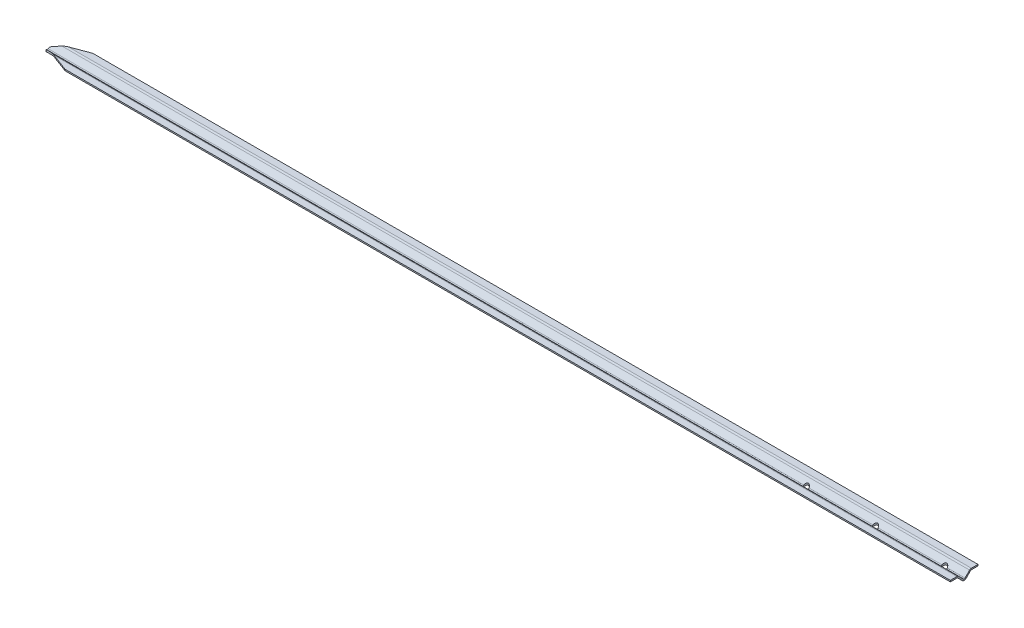
SolidWorks part; units mm, degrees
ref_plane "Спереди" through (0, 0, 0) normal (0, 0, 1) x (1, 0, 0)
ref_plane "Сверху" through (0, 0, 0) normal (0, 1, 0) x (1, 0, 0)
ref_plane "Справа" through (0, 0, 0) normal (1, 0, 0) x (0, 0, -1)
sketch "Эскиз1" plane through (0, 0, 0) normal (1, 0, 0) x (0, 0, -1)
  line L0 (-15, 0) -> (-7, 0)
  line L1 (-7, 0) -> (0, -7)
  line L2 (0, -7) -> (7, 0)
  line L3 (7, 0) -> (15, 0)
  line L4 (0, -3.8182) -> (0, 15.4545) construction
  dimension "D1" = 7
  dimension "D2" = 30
  dimension "D3" = 90
sketch "Эскиз5" plane through (0, 0, 0) normal (1, 0, 0) x (0, 0, -1)
  line L0 (-15, 0) -> (-7, 0) construction
  line L1 (-7, 0) -> (0, -7) construction
  line L2 (0, -7) -> (7, 0) construction
  line L3 (7, 0) -> (15, 0) construction
  line L4 (-15, 0) -> (-7.8284, 0) construction
  line L5 (-6.4142, -0.5858) -> (-1.4142, -5.5858) construction
  line L6 (1.4142, -5.5858) -> (6.4142, -0.5858) construction
  line L7 (7.8284, 0) -> (15, 0) construction
  line L8 (-15, -0.75) -> (-7.8284, -0.75)
  line L9 (-6.9445, -1.1161) -> (-1.9445, -6.1161)
  line L10 (1.9445, -6.1161) -> (6.9445, -1.1161)
  line L11 (7.8284, -0.75) -> (15, -0.75)
  line L12 (-15, 0.75) -> (-7.8284, 0.75)
  line L13 (-5.8839, -0.0555) -> (-0.8839, -5.0555)
  line L14 (0.8839, -5.0555) -> (5.8839, -0.0555)
  line L15 (7.8284, 0.75) -> (15, 0.75)
  line L16 (-15, -0.75) -> (-15, 0.75)
  line L17 (15, -0.75) -> (15, 0.75)
  arc A0 (-7.8284, 0) -> (-6.4142, -0.5858) centre (-7.8284, -2) cw construction
  arc A1 (-1.4142, -5.5858) -> (1.4142, -5.5858) centre (0, -4.1716) ccw construction
  arc A2 (6.4142, -0.5858) -> (7.8284, 0) centre (7.8284, -2) cw construction
  arc A3 (-7.8284, -0.75) -> (-6.9445, -1.1161) centre (-7.8284, -2) cw
  arc A4 (-1.9445, -6.1161) -> (1.9445, -6.1161) centre (0, -4.1716) ccw
  arc A5 (6.9445, -1.1161) -> (7.8284, -0.75) centre (7.8284, -2) cw
  arc A6 (-7.8284, 0.75) -> (-5.8839, -0.0555) centre (-7.8284, -2) cw
  arc A7 (-0.8839, -5.0555) -> (0.8839, -5.0555) centre (0, -4.1716) ccw
  arc A8 (5.8839, -0.0555) -> (7.8284, 0.75) centre (7.8284, -2) cw
  point P36 (-15, 0.75)
  dimension "D1" = 2
  dimension "D2" = 0.75
  dimension "D3" = 0.75
extrude "Бобышка-Вытянуть1" add sketch "Эскиз5" along normal mid plane 1000
sketch "Эскиз2" plane through (0, 0, 0) normal (0, 1, 0) x (1, 0, 0)
  line L0 (-500, 0) -> (-318.2949, 0) construction
  line L2 (-460, -15) -> (-492.5094, -2.809)
  line L3 (-492.5094, 2.809) -> (-460, 15)
  arc A0 (-492.5094, 2.809) -> (-492.5094, -2.809) centre (-491.456, 0) ccw
  point P4 (-485.1451, 0.8839)
  point P7 (-318.2949, -5.8839)
  point P8 (0, 0)
  point P9 (0, 0)
  dimension "D2" = 3
  dimension "D1" = 40
  dimension "D3" = 30
extrude "Вырез-Вытянуть1" cut sketch "Эскиз2" against normal through all and the other way through all
sketch "Эскиз3" plane through (0, 0, 0) normal (0, 1, 0) x (1, 0, 0)
  circle A1 centre (478, 0) radius 3
  circle A2 centre (478, 0) radius 3
  circle A3 centre (328, 0) radius 3
  circle A4 centre (328, 0) radius 3
  circle A5 centre (403, 0) radius 3
  circle A6 centre (403, 0) radius 3
  dimension "D1" = 0
  dimension "D2" = 0
  dimension "D3" = 0
extrude "Вырез-Вытянуть2" cut sketch "Эскиз3" against normal through all
equation "\"D1@Эскиз5\"=\"радиус сгиба\""
equation "\"D3@Эскиз5\"=\"D2@Эскиз5\""
equation "\"длина лезвия\"=1000"
equation "\"радиус острия\"=3"
equation "\"длина острия\"=40"
equation "\"ширина лезвия\"=30"
equation "\"радиус сгиба\"=2"
equation "\"высота ребра жесткости\"=7"
equation "\"тощина\"=1.5"
equation "\"длина рукоятки\"=200"
equation "\"тлщина рукоятки\"=30"
equation "\"диаметр заклепки\"=6"
equation "\"расстояние между заклнпками\"=75"
equation "\"глубина заклепки\"=6"
equation "\"отступ от заклепки\"=3"
equation "\"диаметр шляпы\"=\"диаметр заклепки\" + 2*\"отступ от заклепки\""
equation "\"радиус скруглений\"=5"
equation "\"высота головки\"=1.2"
equation "\"высота купола\"=3"
equation "\"D2@Эскиз5\"=\"тощина\" / 2"
equation "\"D1@Эскиз2\"=\"длина острия\""
equation "\"D2@Эскиз2\"=\"радиус острия\""
equation "\"D3@Эскиз2\"=\"ширина лезвия\""
